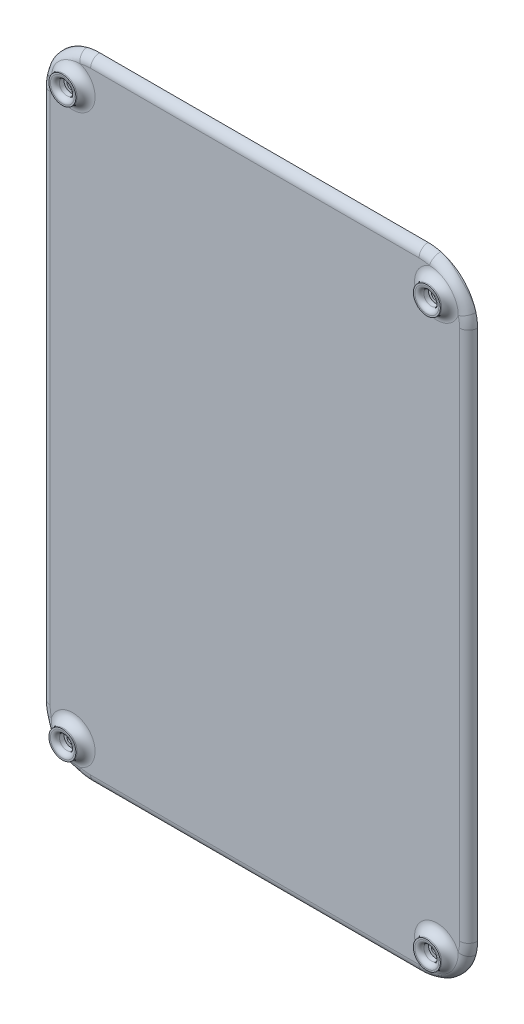
SolidWorks part; units mm, degrees
ref_plane "Front Plane" through (0, 0, 0) normal (0, 0, 1) x (1, 0, 0)
ref_plane "Top Plane" through (0, 0, 0) normal (0, 1, 0) x (1, 0, 0)
ref_plane "Right Plane" through (0, 0, 0) normal (1, 0, 0) x (0, 0, -1)
sketch "Sketch1" plane through (0, 0, 0) normal (0, 0, 1) x (1, 0, 0)
  line L1 (-42.6378, 31.9783) -> (52.3622, 31.9783)
  line L2 (-42.6378, 31.9783) -> (-42.6378, -108.0217)
  line L3 (-42.6378, -108.0217) -> (52.3622, -108.0217)
  line L4 (52.3622, 31.9783) -> (52.3622, -108.0217)
  dimension "D1" = 95
  dimension "D2" = 140
extrude "Boss-Extrude1" add sketch "Sketch1" along normal blind 2
fillet "Fillet1" radius 11 1 edges at (-42.6378, 31.9783, 1) type face fillet first side face at (4.8622, 31.9783, 1) second side face at (-42.6378, -38.0217, 1)
fillet "Fillet2" radius 11 1 edges at (52.3622, 31.9783, 1) type face fillet first side face at (52.3622, -38.0217, 1) second side face at (10.3622, 31.9783, 1)
fillet "Fillet3" radius 11 1 edges at (-42.6378, -108.0217, 1) type face fillet first side face at (-42.6378, -43.5217, 1) second side face at (4.8622, -108.0217, 1)
fillet "Fillet4" radius 11 1 edges at (52.3622, -108.0217, 1) type face fillet first side face at (52.3622, -43.5217, 1) second side face at (10.3622, -108.0217, 1)
sketch "Sketch2" plane through (0, 0, 2) normal (0, 0, 1) x (1, 0, 0)
  line L0 (-42.6378, 20.9783) -> (-42.6378, -97.0217) construction
  line L5 (41.3622, 31.9783) -> (-31.6378, 31.9783) construction
  line L6 (-31.6378, -108.0217) -> (41.3622, -108.0217) construction
  line L7 (52.3622, -97.0217) -> (52.3622, 20.9783) construction
  line L8 (4.8622, 31.9783) -> (4.8622, -108.0217) construction
  line L9 (-42.6378, -38.0217) -> (52.3622, -38.0217) construction
  circle A0 centre (-35.6378, 24.9783) radius 1
  circle A1 centre (-35.6378, 24.9783) radius 3
  circle A2 centre (45.3622, 24.9783) radius 1
  circle A3 centre (45.3622, 24.9783) radius 3
  circle A4 centre (45.3622, -101.0217) radius 1
  circle A5 centre (45.3622, -101.0217) radius 3
  circle A6 centre (-35.6378, -101.0217) radius 3
  circle A7 centre (-35.6378, -101.0217) radius 1
  dimension "D1" = 81
extrude "Boss-Extrude2" add sketch "Sketch2" along normal blind 2.2766
sketch "Sketch3" plane through (0, 0, 2) normal (0, 0, 1) x (1, 0, 0)
  circle A0 centre (-35.6378, 24.9783) radius 1
  circle A1 centre (45.3622, 24.9783) radius 1
  circle A2 centre (45.3622, -101.0217) radius 1
  circle A3 centre (-35.6378, -101.0217) radius 1
extrude "Cut-Extrude1" cut sketch "Sketch3" against normal blind 3
fillet "Fillet5" radius 2 1 edges at (-38.6378, -101.0217, 2) type face fillet first side face at (-38.6378, -101.0217, 2) second side face at (-38.6378, -101.0217, 4.2766)
fillet "Fillet6" radius 2 1 edges at (42.3622, 24.9783, 2) type face fillet first side face at (42.3622, 24.9783, 4.2766) second side face at (-30.6378, -101.0217, 2)
fillet "Fillet7" radius 2 1 edges at (48.3622, -101.0217, 2) type face fillet first side face at (50.3622, 24.9783, 2) second side face at (48.3622, -101.0217, 4.2766)
fillet "Fillet8" radius 2 1 edges at (-32.6378, 24.9783, 2) type face fillet first side face at (50.3622, -101.0217, 2) second side face at (-32.6378, 24.9783, 4.2766)
sketch "Sketch6" plane through (0, 0, 4.2766) normal (0, 0, 1) x (1, 0, 0)
  line L0 (4.8622, -108.0217) -> (4.8622, 31.9783) construction
  line L1 (-31.6378, -108.0217) -> (41.3622, -108.0217) construction
  line L2 (41.3622, 31.9783) -> (-31.6378, 31.9783) construction
  line L3 (-42.6378, -38.0217) -> (52.3622, -38.0217) construction
  line L4 (-42.6378, 20.9783) -> (-42.6378, -97.0217) construction
  line L5 (52.3622, -97.0217) -> (52.3622, 20.9783) construction
  circle A0 centre (-35.6378, -101.0217) radius 1.65
  circle A1 centre (45.3622, -101.0217) radius 1.65
  circle A2 centre (45.3622, 24.9783) radius 1.65
  circle A3 centre (-35.6378, 24.9783) radius 1.65
extrude "Cut-Extrude3" cut sketch "Sketch6" against normal blind 2
fillet "Fillet9" radius 1 1 edges at (-33.9878, -101.0217, 4.2766) type face fillet first side face at (-33.9878, -101.0217, 4.2766) second side face at (-33.9878, -101.0217, 2.2766)
fillet "Fillet10" radius 1 1 edges at (43.7122, -101.0217, 4.2766) type face fillet first side face at (43.7122, -101.0217, 2.2766) second side face at (43.7122, -101.0217, 4.2766)
fillet "Fillet11" radius 1 1 edges at (-37.2878, 24.9783, 4.2766) type face fillet first side face at (-37.2878, 24.9783, 4.2766) second side face at (-37.2878, 24.9783, 2.2766)
fillet "Fillet12" radius 1 1 edges at (47.0122, 24.9783, 4.2766) type face fillet first side face at (47.0122, 24.9783, 2.2766) second side face at (47.0122, 24.9783, 4.2766)
fillet "Fillet13" radius 2 1 edges at (-42.6378, -38.0217, 2) type face fillet first side face at (-30.6378, 24.9783, 2) second side face at (-42.6378, -38.0217, 1)
